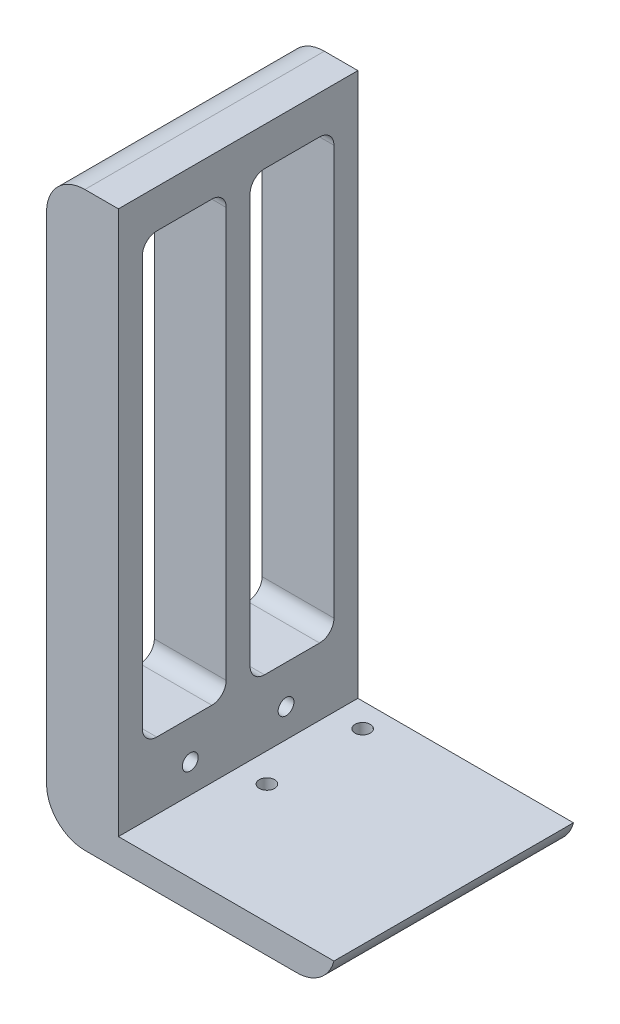
SolidWorks part; units mm, degrees
ref_plane "前视基准面" through (0, 0, 0) normal (0, 0, 1) x (1, 0, 0)
ref_plane "上视基准面" through (0, 0, 0) normal (0, 1, 0) x (1, 0, 0)
ref_plane "右视基准面" through (0, 0, 0) normal (1, 0, 0) x (0, 0, -1)
other "Configuration Table"
sketch "草图1" plane through (0, 0, 0) normal (0, 0, 1) x (1, 0, 0)
  line L0 (0, 0) -> (0, 119.5)
  line L1 (0, 119.5) -> (15, 119.5)
  line L2 (15, 119.5) -> (15, 6)
  line L3 (15, 6) -> (60, 6)
  line L4 (60, 6) -> (60, 0)
  line L5 (60, 0) -> (0, 0)
  dimension "D1" = 6
  dimension "D2" = 15
  dimension "D3" = 60
  dimension "D4" = 119.5
extrude "凸台-拉伸1" add sketch "草图1" along normal mid plane 50
fillet "圆角1" radius 8 3 edges at (0, 119.5, 0) (60, 0, 0) (0, 0, 0)
sketch "草图2" plane through (0, 0, 0) normal (-1, 0, 0) x (0, 0, 1)
  line L0 (0, 0) -> (0, 33.7003) construction
  line L2 (25, 0) -> (-25, 0) construction
  circle A0 centre (10, 12) radius 1.65
  circle A1 centre (-10, 12) radius 1.65
  dimension "D1" = 3.3
  dimension "D2" = 12
  dimension "D3" = 20
extrude "切除-拉伸1" cut sketch "草图2" against normal through all
sketch "草图3" plane through (0, 6, 0) normal (0, 1, 0) x (1, 0, 0)
  line L0 (21, 20) -> (21, 0) construction
  line L1 (60, 25) -> (15, 25) construction
  circle A0 centre (21, 0) radius 1.6
  circle A1 centre (21, 20) radius 1.6
  dimension "D1" = 3.2
  dimension "D2" = 20
  dimension "D3" = 5
  dimension "D4" = 21
extrude "切除-拉伸2" cut sketch "草图3" against normal through all
sketch "草图4" plane through (0, 0, 0) normal (-1, 0, 0) x (0, 0, 1)
  line L0 (-20, 111.5) -> (-20, 20)
  line L1 (-20, 20) -> (-2.5, 20)
  line L2 (-2.5, 20) -> (-2.5, 111.5)
  line L3 (-2.5, 111.5) -> (-20, 111.5)
  line L4 (0, 0) -> (0, 123.1134) construction
  line L5 (25, 0) -> (-25, 0) construction
  line L6 (-25, 111.5) -> (-25, 8) construction
  line L7 (-25, 119.5) -> (25, 119.5) construction
  line L8 (2.5, 111.5) -> (20, 111.5)
  line L9 (2.5, 20) -> (2.5, 111.5)
  line L10 (20, 20) -> (2.5, 20)
  line L11 (20, 111.5) -> (20, 20)
  dimension "D1" = 5
  dimension "D2" = 5
  dimension "D3" = 8
  dimension "D4" = 20
extrude "切除-拉伸3" cut sketch "草图4" against normal through all
fillet "圆角2" radius 3 8 edges at (7.5, 111.5, -2.5) (7.5, 111.5, -20) (7.5, 111.5, 20) (7.5, 111.5, 2.5) (7.5, 20, 20) (7.5, 20, 2.5) (7.5, 20, -20) (7.5, 20, -2.5)
